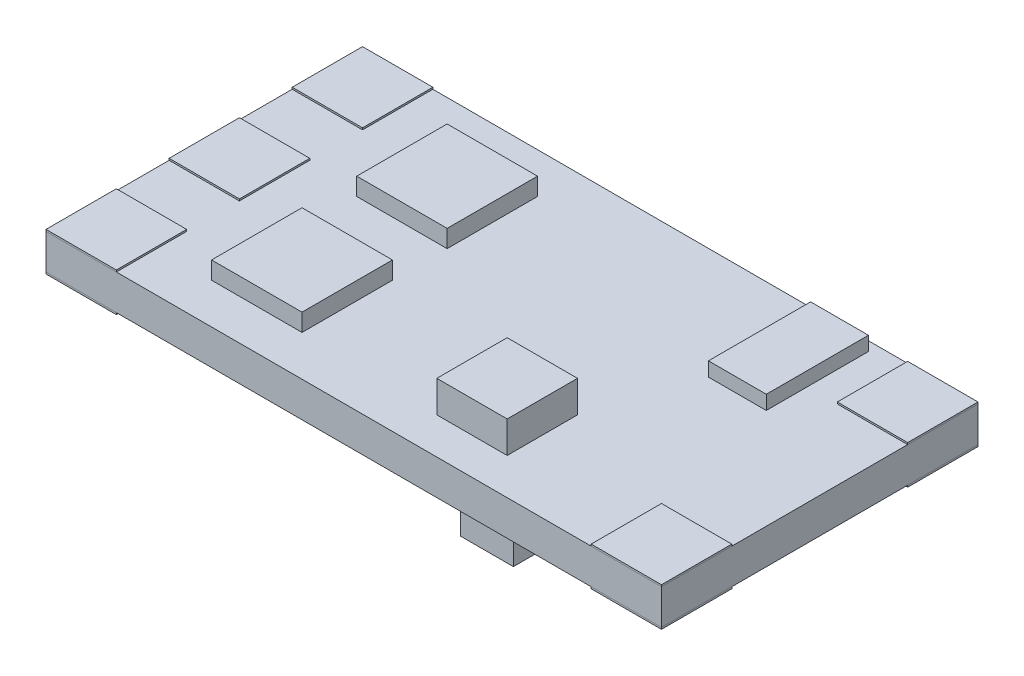
SolidWorks part; units mm, degrees
ref_plane "Front Plane" through (0, 0, 0) normal (0, 0, 1) x (1, 0, 0)
ref_plane "Top Plane" through (0, 0, 0) normal (0, 1, 0) x (1, 0, 0)
ref_plane "Right Plane" through (0, 0, 0) normal (1, 0, 0) x (0, 0, -1)
sketch "Sketch1" plane through (0, 0, 0) normal (0, 1, 0) x (1, 0, 0)
  line L1 (-17.5, -9) -> (17.5, -9)
  line L2 (-17.5, -9) -> (-17.5, 9)
  line L3 (-17.5, 9) -> (17.5, 9)
  line L4 (17.5, -9) -> (17.5, 9)
  line L5 (0, 9) -> (0, -9) construction
  line L6 (-17.5, 0) -> (17.5, 0) construction
  point P0 (0, 0)
  dimension "D1" = 35
  dimension "D2" = 18
extrude "Boss-Extrude1" add sketch "Sketch1" along normal blind 2
sketch "Sketch2" plane through (0, 2, 0) normal (0, 1, 0) x (1, 0, 0)
  line L1 (8.5094, 2.6608) -> (11.8, 2.6608)
  line L2 (8.5094, 2.6608) -> (8.5094, 8.4708)
  line L3 (8.5094, 8.4708) -> (11.8, 8.4708)
  line L4 (11.8, 2.6608) -> (11.8, 8.4708)
  line L5 (10.1547, 8.4708) -> (10.1547, 2.6608) construction
  line L6 (8.5094, 5.5658) -> (11.8, 5.5658) construction
  point P0 (10.1547, 5.5658)
extrude "Boss-Extrude2" add sketch "Sketch2" along normal blind 0.8 separate body
sketch "Sketch3" plane through (0, 2, 0) normal (0, 1, 0) x (1, 0, 0)
  line L1 (2.6479, -6.9231) -> (6.6479, -6.9231)
  line L2 (2.6479, -6.9231) -> (2.6479, -2.9231)
  line L3 (2.6479, -2.9231) -> (6.6479, -2.9231)
  line L4 (6.6479, -6.9231) -> (6.6479, -2.9231)
  line L5 (4.6479, -2.9231) -> (4.6479, -6.9231) construction
  line L6 (2.6479, -4.9231) -> (6.6479, -4.9231) construction
  point P0 (4.6479, -4.9231)
  dimension "D1" = 4
extrude "Boss-Extrude3" add sketch "Sketch3" along normal blind 1.8 separate body
sketch "Sketch4" plane through (0, 2, 0) normal (0, 1, 0) x (1, 0, 0)
  line L0 (-17.5, 0) -> (17.5, 0) construction
  line L5 (-17.5, 9) -> (-17.5, -9) construction
  line L6 (17.5, -9) -> (17.5, 9) construction
  line L7 (-10.3861, -6.697) -> (-5.2444, -6.697)
  line L8 (-10.3861, -6.697) -> (-10.3861, -1.5553)
  line L9 (-10.3861, -1.5553) -> (-5.2444, -1.5553)
  line L10 (-5.2444, -6.697) -> (-5.2444, -1.5553)
  line L11 (-7.8153, -1.5553) -> (-7.8153, -6.697) construction
  line L12 (-10.3861, -4.1261) -> (-5.2444, -4.1261) construction
  line L13 (-10.3861, 1.5553) -> (-5.2444, 1.5553)
  line L14 (-5.2444, 6.697) -> (-5.2444, 1.5553)
  line L15 (-10.3861, 6.697) -> (-5.2444, 6.697)
  line L16 (-10.3861, 6.697) -> (-10.3861, 1.5553)
  point P4 (-7.8153, -4.1261)
extrude "Boss-Extrude4" add sketch "Sketch4" along normal blind 1 separate body
sketch "Sketch5" plane through (0, 2, 0) normal (0, 1, 0) x (1, 0, 0)
  line L0 (-17.5, 9) -> (-17.5, -9) construction
  line L1 (-13.5, 5) -> (-17.5, 5)
  line L2 (-13.5, 5) -> (-13.5, 9)
  line L3 (-13.5, 9) -> (-17.5, 9)
  line L4 (-17.5, 5) -> (-17.5, 9)
  line L5 (-15.5, 9) -> (-15.5, 5) construction
  line L6 (-13.5, 7) -> (-17.5, 7) construction
  line L7 (-13.5, -2) -> (-17.5, -2)
  line L8 (-13.5, -2) -> (-13.5, 2)
  line L9 (-13.5, 2) -> (-17.5, 2)
  line L10 (-17.5, -2) -> (-17.5, 2)
  line L11 (-15.5, 2) -> (-15.5, -2) construction
  line L12 (-13.5, 0) -> (-17.5, 0) construction
  line L13 (13.5, -9) -> (17.5, -9)
  line L14 (-13.5, -5) -> (-17.5, -5)
  line L15 (-13.5, -5) -> (-13.5, -9)
  line L16 (-13.5, -9) -> (-17.5, -9)
  line L17 (-17.5, -5) -> (-17.5, -9)
  line L18 (-15.5, -9) -> (-15.5, -5) construction
  line L19 (-13.5, -7) -> (-17.5, -7) construction
  line L20 (13.5, 5) -> (17.5, 5)
  line L21 (13.5, 5) -> (13.5, 9)
  line L22 (13.5, 9) -> (17.5, 9)
  line L23 (17.5, 5) -> (17.5, 9)
  line L24 (15.5, 9) -> (15.5, 5) construction
  line L25 (13.5, 7) -> (17.5, 7) construction
  line L26 (17.5, -5) -> (17.5, -9)
  line L27 (13.5, -5) -> (17.5, -5)
  line L28 (13.5, -5) -> (13.5, -9)
  point P0 (-15.5, 7)
  point P4 (-15.5, 0)
  point P10 (-15.5, -7)
  point P14 (15.5, 7)
  point P18 (0, 0)
  dimension "D1" = 4
extrude "Boss-Extrude5" add sketch "Sketch5" along normal blind 0.1 separate body
ref_plane "Plane1" through (0, 1, 0) normal (0, 1, 0) x (1, 0, 0)
mirror "Mirror1" about plane through (0, 1, 0) normal (0, 1, 0) of bodies 106 107 108 109 110
sketch "Sketch6" plane through (0, 0, 0) normal (0, -1, 0) x (1, 0, 0)
  line L0 (-4, 9) -> (-4, -9) construction
  line L1 (-17.5, 9) -> (17.5, 9) construction
  line L2 (17.5, -9) -> (-17.5, -9) construction
  line L3 (-17.5, -9) -> (-17.5, 9) construction
  line L4 (-11.5, -8.238) -> (-4.8052, -8.238)
  line L5 (-11.5, 3.762) -> (-4.8052, 3.762)
  line L6 (-11.5, 3.762) -> (-11.5, 8.238)
  line L7 (-11.5, 8.238) -> (-4.8052, 8.238)
  line L8 (-4.8052, 3.762) -> (-4.8052, 8.238)
  line L9 (-8.1526, 8.238) -> (-8.1526, 3.762) construction
  line L10 (-11.5, 6) -> (-4.8052, 6) construction
  line L11 (-11.5, -2.238) -> (-4.8052, -2.238)
  line L12 (-11.5, -2.238) -> (-11.5, 2.238)
  line L13 (-11.5, 2.238) -> (-4.8052, 2.238)
  line L14 (-4.8052, -2.238) -> (-4.8052, 2.238)
  line L15 (-8.1526, 2.238) -> (-8.1526, -2.238) construction
  line L16 (-11.5, 0) -> (-4.8052, 0) construction
  line L17 (-4.8052, -3.762) -> (-4.8052, -8.238)
  line L18 (-11.5, -3.762) -> (-4.8052, -3.762)
  line L19 (-11.5, -3.762) -> (-11.5, -8.238)
  line L20 (3.5, -3.762) -> (3.5, -8.238)
  line L21 (3.5, -3.762) -> (-3.1948, -3.762)
  line L22 (-3.1948, -3.762) -> (-3.1948, -8.238)
  line L23 (3.5, -8.238) -> (-3.1948, -8.238)
  line L24 (3.5, 2.238) -> (-3.1948, 2.238)
  line L25 (-3.1948, -2.238) -> (-3.1948, 2.238)
  line L26 (3.5, -2.238) -> (-3.1948, -2.238)
  line L27 (3.5, -2.238) -> (3.5, 2.238)
  line L28 (3.5, 8.238) -> (-3.1948, 8.238)
  line L29 (-3.1948, 3.762) -> (-3.1948, 8.238)
  line L30 (3.5, 3.762) -> (-3.1948, 3.762)
  line L31 (3.5, 3.762) -> (3.5, 8.238)
  point P8 (-8.1526, 6)
  point P12 (-8.1526, 0)
  point P16 (-4.8052, 3.762)
  dimension "D1" = 13.5
  dimension "D2" = 6
  dimension "D3" = 6
extrude "Boss-Extrude6" add sketch "Sketch6" along normal blind 0.7 separate body
sketch "Sketch7" plane through (0, 0, 0) normal (0, -1, 0) x (1, 0, 0)
  line L0 (7, 9) -> (7, -9) construction
  line L1 (-17.5, 9) -> (17.5, 9) construction
  line L2 (17.5, -9) -> (-17.5, -9) construction
  line L3 (17.5, 9) -> (17.5, -9) construction
  line L4 (5.5, 4.6444) -> (5.5, 6.2444)
  line L5 (5.5, 6.8222) -> (8.5, 6.8222)
  line L6 (5.5, 6.8222) -> (5.5, 8.4222)
  line L7 (5.5, 8.4222) -> (8.5, 8.4222)
  line L8 (8.5, 6.8222) -> (8.5, 8.4222)
  line L9 (7, 8.4222) -> (7, 6.8222) construction
  line L10 (5.5, 7.6222) -> (8.5, 7.6222) construction
  line L11 (5.5, 4.6444) -> (8.5, 4.6444)
  line L12 (8.5, 4.6444) -> (8.5, 6.2444)
  line L13 (5.5, 6.2444) -> (8.5, 6.2444)
  line L14 (5.5, 2.4667) -> (5.5, 4.0667)
  line L15 (5.5, 2.4667) -> (8.5, 2.4667)
  line L16 (8.5, 2.4667) -> (8.5, 4.0667)
  line L17 (5.5, 4.0667) -> (8.5, 4.0667)
  line L18 (5.5, 0.2889) -> (5.5, 1.8889)
  line L19 (5.5, 0.2889) -> (8.5, 0.2889)
  line L20 (8.5, 0.2889) -> (8.5, 1.8889)
  line L21 (5.5, 1.8889) -> (8.5, 1.8889)
  line L22 (5.5, -1.8889) -> (5.5, -0.2889)
  line L23 (5.5, -1.8889) -> (8.5, -1.8889)
  line L24 (8.5, -1.8889) -> (8.5, -0.2889)
  line L25 (5.5, -0.2889) -> (8.5, -0.2889)
  line L26 (5.5, -4.0667) -> (5.5, -2.4667)
  line L27 (5.5, -4.0667) -> (8.5, -4.0667)
  line L28 (8.5, -4.0667) -> (8.5, -2.4667)
  line L29 (5.5, -2.4667) -> (8.5, -2.4667)
  line L30 (5.5, -6.2444) -> (5.5, -4.6444)
  line L31 (5.5, -6.2444) -> (8.5, -6.2444)
  line L32 (8.5, -6.2444) -> (8.5, -4.6444)
  line L33 (5.5, -4.6444) -> (8.5, -4.6444)
  line L34 (5.5, -8.4222) -> (5.5, -6.8222)
  line L35 (5.5, -8.4222) -> (8.5, -8.4222)
  line L36 (8.5, -8.4222) -> (8.5, -6.8222)
  line L37 (5.5, -6.8222) -> (8.5, -6.8222)
  line L38 (8.5, -8.4222) -> (8.5, -9) construction
  line L39 (8.5, 8.4222) -> (8.5, 9) construction
  line L40 (8.5, 6.8222) -> (8.5, 6.2444) construction
  point P8 (7, 7.6222)
  dimension "D1" = 10.5
  dimension "D3" = 1.6
  dimension "D4" = 3
  dimension "D2" = 8
extrude "Boss-Extrude7" add sketch "Sketch7" along normal blind 1.8 separate body
